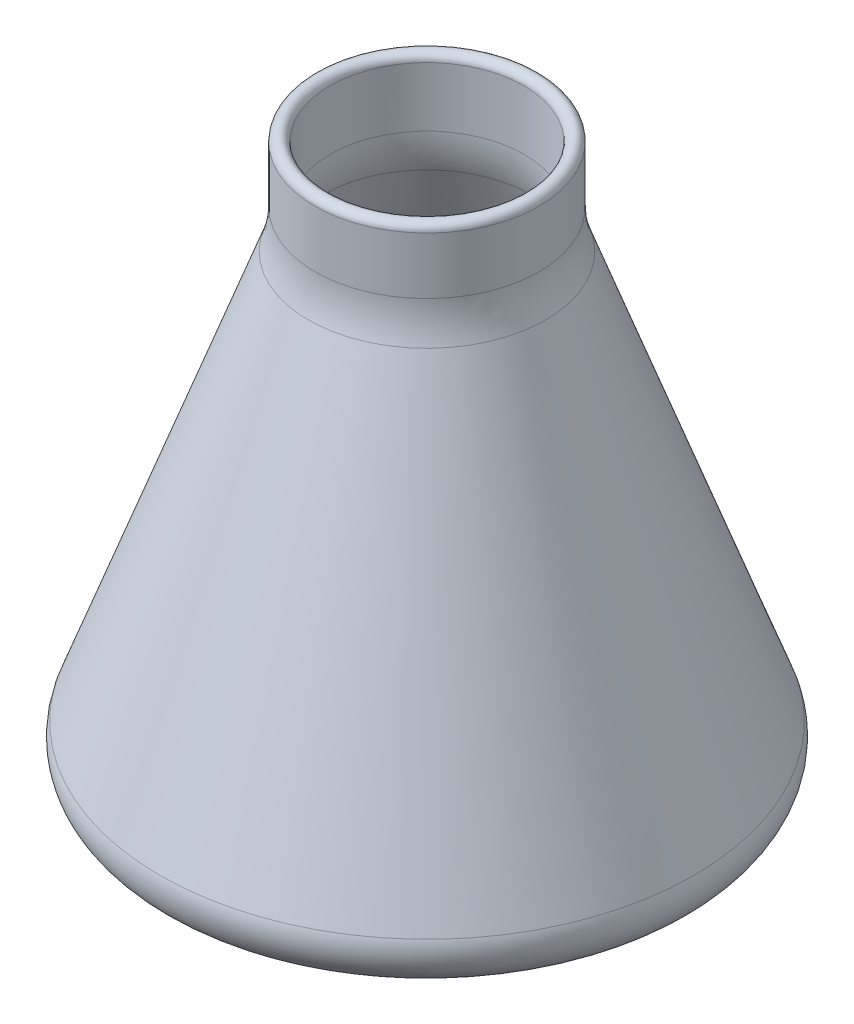
SolidWorks part; units mm, degrees
ref_plane "Front Plane" through (0, 0, 0) normal (0, 0, 1) x (1, 0, 0)
ref_plane "Top Plane" through (0, 0, 0) normal (0, 1, 0) x (1, 0, 0)
ref_plane "Right Plane" through (0, 0, 0) normal (1, 0, 0) x (0, 0, -1)
sketch "Sketch1" plane through (0, 0, 0) normal (0, 0, 1) x (1, 0, 0)
  line L0 (0, 0) -> (0, 300)
  line L1 (0, 300) -> (60, 300)
  line L2 (60, 300) -> (60, 255)
  line L3 (60, 255) -> (152.8124, 0)
  line L4 (152.8124, 0) -> (0, 0)
  dimension "D1" = 300
  dimension "D2" = 60
  dimension "D3" = 45
  dimension "D4" = 20
revolve "Revolve2" add sketch "Sketch1" angle 360 about L0
shell "Shell1" thickness 8
fillet "Fillet1" radius 4 2 edges at (0, 300, 52) (0, 300, -60)
fillet "Fillet2" radius 60 2 edges at (0, 253.5894, -52) (0, 255, -60)
fillet "Fillet3" radius 20 2 edges at (0, 12, -139.9313) (0, 0, -152.8124)
